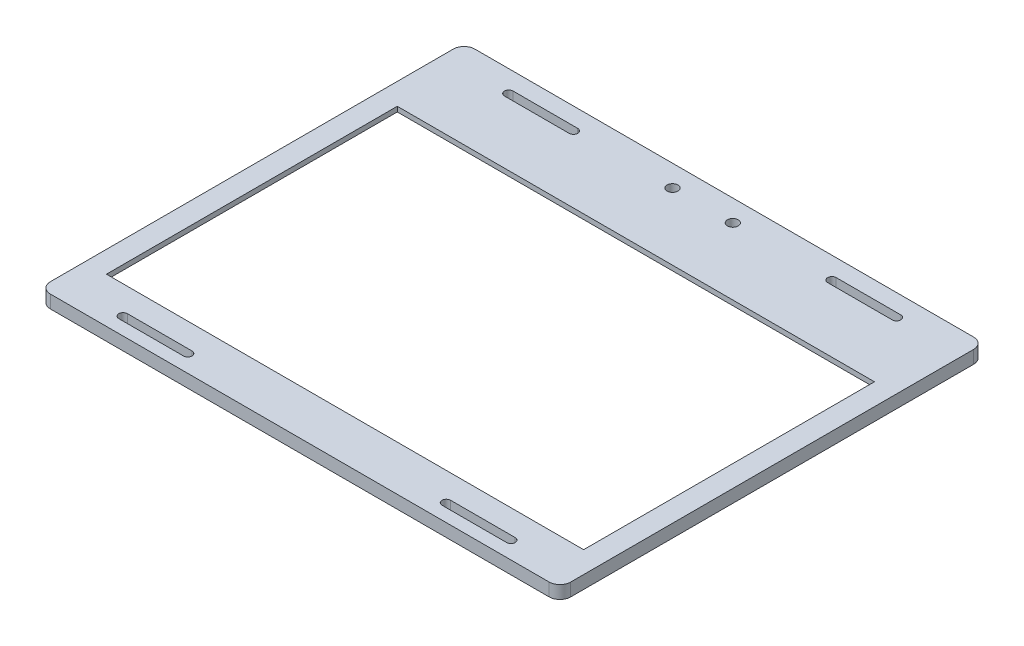
SolidWorks part; units mm, degrees
note: The reader was unsure of these and kept them because the rebuilt part matched: shared geometry of "Sketch1<5>".
ref_plane "Front Plane" through (0, 0, 0) normal (0, 0, 1) x (1, 0, 0)
ref_plane "Top Plane" through (0, 0, 0) normal (0, 1, 0) x (1, 0, 0)
ref_plane "Right Plane" through (0, 0, 0) normal (1, 0, 0) x (0, 0, -1)
sketch "Sketch1" plane through (0, 0, 0) normal (0, 1, 0) x (1, 0, 0)
  line L0 (120.75, 81) -> (120.75, -81)
  line L1 (-114.75, 75) -> (114.75, 75)
  line L2 (-114.75, 75) -> (-114.75, -75)
  line L3 (-114.75, -75) -> (114.75, -75)
  line L4 (114.75, 75) -> (114.75, -75)
  line L5 (-114.75, 75) -> (114.75, -75) construction
  line L6 (-114.75, -75) -> (114.75, 75) construction
  line L7 (-120.75, -81) -> (120.75, -81)
  line L8 (-120.75, 81) -> (-120.75, -81)
  line L9 (-120.75, 81) -> (120.75, 81)
  line L10 (-112.75, -73) -> (112.75, -73)
  line L11 (112.75, 73) -> (112.75, -73)
  line L12 (-112.75, 73) -> (112.75, 73)
  line L13 (-112.75, 73) -> (-112.75, -73)
  line L14 (75, 91) -> (-75, 91) construction
  line L15 (-120.75, 81) -> (120.75, 81)
  line L16 (-120.75, 81) -> (-120.75, 101)
  line L17 (-120.75, 101) -> (120.75, 101)
  line L18 (120.75, 81) -> (120.75, 101)
  line L19 (-90, 91) -> (-60, 91) construction
  line L20 (-120.75, -81) -> (120.75, -81)
  line L21 (-120.75, -81) -> (-120.75, -96)
  line L22 (-120.75, -96) -> (120.75, -96)
  line L23 (120.75, -81) -> (120.75, -96)
  line L24 (-90, 93) -> (-60, 93)
  line L25 (-90, 89) -> (-60, 89)
  line L26 (0, -96) -> (0, 101) construction
  line L27 (90, 91) -> (60, 91) construction
  line L28 (90, 93) -> (60, 93)
  line L29 (90, 89) -> (60, 89)
  line L30 (-90, -88) -> (-60, -88) construction
  line L31 (-90, -86) -> (-60, -86)
  line L32 (-90, -90) -> (-60, -90)
  line L33 (90, -88) -> (60, -88) construction
  line L34 (90, -86) -> (60, -86)
  line L35 (90, -90) -> (60, -90)
  circle A2 centre (-14, 91) radius 2.5
  circle A3 centre (14, 91) radius 2.5
  arc A4 (-90, 93) -> (-90, 89) centre (-90, 91) ccw
  arc A5 (-60, 89) -> (-60, 93) centre (-60, 91) ccw
  arc A6 (90, 93) -> (90, 89) centre (90, 91) cw
  arc A7 (60, 89) -> (60, 93) centre (60, 91) cw
  arc A8 (-90, -86) -> (-90, -90) centre (-90, -88) ccw
  arc A9 (-60, -90) -> (-60, -86) centre (-60, -88) ccw
  arc A10 (90, -86) -> (90, -90) centre (90, -88) cw
  arc A11 (60, -90) -> (60, -86) centre (60, -88) cw
  point P0 (0, 0)
  point P6 (-75, 91)
  point P18 (-75, -88)
  point P20 (0, 91)
  point P21 (120.75, 91)
  point P40 (75, 91)
  point P53 (75, -88)
  dimension "D6" = 4
  dimension "D8" = 28
  dimension "D9" = 5
  dimension "D1" = 229.5
  dimension "D2" = 150
  dimension "D5" = 20
  dimension "D7" = 150
  dimension "D10" = 15
  dimension "D11" = 4
  dimension "D12" = 30
  dimension "D13" = 30
  dimension "D14" = 8
  dimension "D3" = 6
  dimension "D4" = 2
extrude "Boss-Extrude1" add sketch "Sketch1" along normal blind 6
extrude "Cut-Extrude1" cut sketch "Sketch1<5>" along normal blind 3.7 contours L1 L4 L3 L2
sketch "Sketch1<5>" plane through (0, 0, 0) normal (0, 1, 0) x (1, 0, 0) same geometry as "Sketch1"
fillet "Fillet1" radius 5 4 edges at (120.75, 3, -101) (-120.75, 3, -101) (120.75, 3, 96) (-120.75, 3, 96)
sketch "Sketch2" plane through (0, 3.7, 0) normal (0, -1, 0) x (1, 0, 0)
  line L1 (114.75, -75) -> (94.75, -75)
  line L2 (114.75, -75) -> (114.75, -60)
  line L3 (114.75, -60) -> (94.75, -60)
  line L4 (-114.75, 75) -> (-114.75, -75)
  line L5 (-114.75, -75) -> (114.75, -75)
  line L6 (114.75, -75) -> (114.75, 75)
  line L7 (114.75, 75) -> (-114.75, 75)
  line L8 (-114.75, 75) -> (-114.75, -75)
  line L9 (-114.75, -75) -> (114.75, -75)
  line L10 (114.75, -75) -> (114.75, 75)
  line L11 (114.75, 75) -> (-114.75, 75)
  line L13 (114.75, 75) -> (94.75, 75)
  line L14 (114.75, 75) -> (114.75, 70)
  line L17 (-114.75, 75) -> (-94.75, 75)
  line L18 (-114.75, 75) -> (-114.75, 70)
  line L21 (-114.75, -75) -> (-94.75, -75)
  line L22 (-114.75, -75) -> (-114.75, -60)
  line L23 (-114.75, -60) -> (94.75, -60)
  line L25 (110.75, 75) -> (110.75, -60)
  line L26 (-110.75, 75) -> (-110.75, -75)
  dimension "D2" = 15
  dimension "D3" = 4
  dimension "D4" = 4
  dimension "D1" = 0
extrude "Cut-Extrude3" cut sketch "Sketch2" against normal through all both and the other way through all
